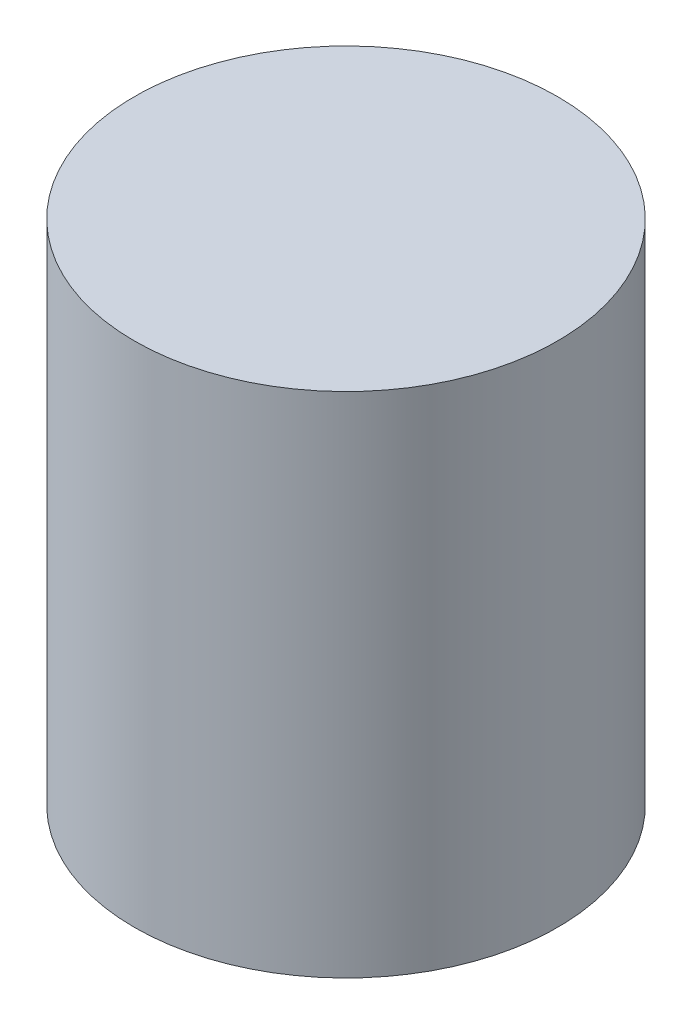
SolidWorks part; units mm, degrees
material "Silicon"
ref_plane "Front Plane" through (0, 0, 0) normal (0, 0, 1) x (1, 0, 0)
ref_plane "Top Plane" through (0, 0, 0) normal (0, 1, 0) x (1, 0, 0)
ref_plane "Right Plane" through (0, 0, 0) normal (1, 0, 0) x (0, 0, -1)
sketch "Sketch2" plane through (0, 0, 0) normal (0, 1, 0) x (1, 0, 0)
  circle A0 centre (0, 0) radius 63.5
  dimension "D1" = 127
extrude "Boss-Extrude1" add sketch "Sketch2" along normal blind 152.4
equation "\"PackedDiameter\" = 5"
equation "\"PackedLength\"= 6"
equation "\"D1@Sketch2\"=\"PackedDiameter\""
equation "\"D1@Boss-Extrude1\"=\"PackedLength\""
